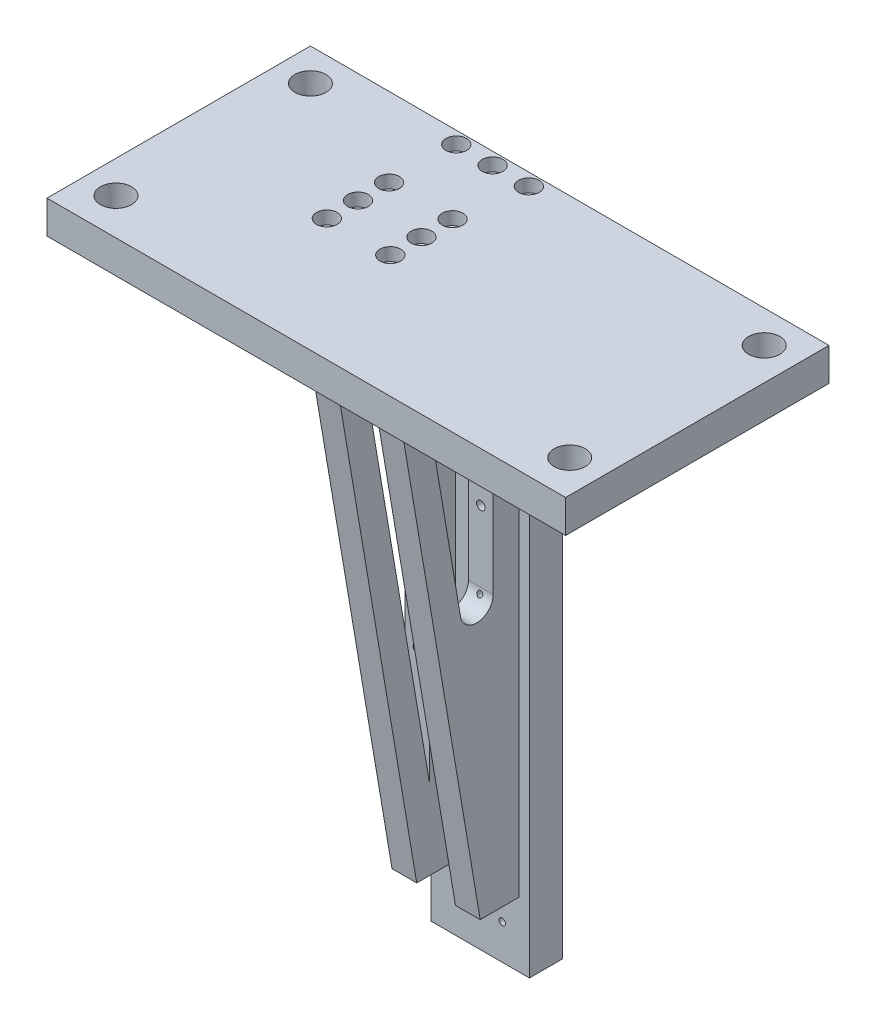
SolidWorks part; units mm, degrees
other "IGNORE"
ref_plane "Front Plane" through (0, 0, 0) normal (0, 0, 1) x (1, 0, 0)
ref_plane "Top Plane" through (0, 0, 0) normal (0, 1, 0) x (1, 0, 0)
ref_plane "Right Plane" through (0, 0, 0) normal (1, 0, 0) x (0, 0, -1)
sketch "Sketch1" plane through (0, 0, 0) normal (1, 0, 0) x (0, 0, -1)
  line L0 (-92.075, 0) -> (9.525, 0)
  line L2 (0, 0) -> (9.525, 0)
  line L4 (9.525, 9.525) -> (-92.075, 9.525)
  line L5 (-92.075, 9.525) -> (-92.075, 0)
  line L7 (0, 0) -> (9.525, 0)
  line L8 (0, 0) -> (0, -250)
  line L9 (0, -250) -> (9.525, -250)
  line L10 (9.525, 0) -> (9.525, -250)
  line L16 (9.525, 9.525) -> (9.525, 0)
  line L17 (-5.005, 0) -> (-5.005, -3.175)
  line L19 (-92.075, 0) -> (-92.075, -3.175)
  line L20 (-92.075, -3.175) -> (9.525, -3.175)
  dimension "D1" = 9.525
  dimension "D2" = 9.525
  dimension "D3" = 101.6
  dimension "D5" = 250
  dimension "D7" = 12.7
  dimension "14.53" = 14.53
extrude "Boss-Extrude5" add sketch "Sketch1" along normal blind 125 and the other way blind 75 contours L16 L4 L5 L0 | L19 L20 L17 L0 region at (0, 4.7625, 41.275) region at (0, -1.5875, 48.54)
extrude "Boss-Extrude6" add sketch "Sketch1<5>" along normal mid plane 38 separate body contours L10 L0 L8 L9 | L8 L20 L10 L0 region at (0, -1.5875, -4.7625) region at (0, -126.5875, -4.7625)
sketch "Sketch1<5>" plane through (0, 0, 0) normal (1, 0, 0) x (0, 0, -1) same geometry as "Sketch1"
sketch "Sketch2" plane through (0, 0, -9.525) normal (0, 0, -1) x (-1, 0, 0)
  line L0 (0, 0) -> (0, -263.8174) construction
  line L1 (-19, 0) -> (-15, 0)
  line L2 (-15, -4.5282) -> (15, -4.5282)
  line L3 (-15, -4.5282) -> (-15, -36.0894)
  line L4 (-15, -36.0894) -> (15, -36.0894)
  line L5 (15, -4.5282) -> (15, -36.0894)
  line L6 (-19, 0) -> (19, 0) construction
  line L7 (-15, 0) -> (-15, -250)
  line L8 (-19, -250) -> (19, -250) construction
  line L9 (-15, -250) -> (-19, -250)
  line L10 (-19, -250) -> (-19, 0)
  line M8 (19, 0) -> (-19, 0)
  line M9 (-19, 0) -> (-19, -250)
  line M10 (-19, -250) -> (19, -250)
  dimension "D1" = 30
  dimension "D2" = 4
extrude "Boss-Extrude7" add sketch "Sketch2" along normal blind 3.175 contours L7 L3 M8 M9 M10 region at (17, -125, -9.525)
sketch "Sketch6" plane through (0, 0, 0) normal (0, -1, 0) x (1, 0, 0)
  line L0 (19, 0) -> (-19, 0) construction
  line L1 (-10, 5.005) -> (10, 5.005)
  line L2 (-10, 5.005) -> (-10, 0)
  line L3 (-10, 0) -> (10, 0)
  line L4 (10, 5.005) -> (10, 0)
  line L5 (0, 0) -> (0, 18.4937) construction
  line L6 (0, -9.525) -> (0, 92.075) construction
  line L7 (19, 0) -> (19, -12.7) construction
  line L8 (19, -2.525) -> (24, -2.525)
  line L9 (19, -2.525) -> (19, -7.525)
  line L10 (19, -7.525) -> (24, -7.525)
  line L11 (24, -2.525) -> (24, -7.525)
  line L12 (-75, -9.525) -> (125, -9.525) construction
  line L13 (-75, 5.005) -> (125, 5.005) construction
  dimension "D2" = 20
  dimension "D3" = 2
  dimension "D4" = 5
  dimension "D5" = 5
extrude "Boss-Extrude8" add sketch "Sketch6" along normal up to vertex (3.175 mm away) up to point (0, -3.175, 92.075)
sketch "Sketch3" plane through (0, 0, 0) normal (0, 1, 0) x (1, 0, 0)
  line L0 (0, 0) -> (0, 9.525) construction
  line L1 (-19, 4.7625) -> (19, 4.7625) construction
  line L2 (-19, 0) -> (-19, 9.525) construction
  line L3 (19, 0) -> (19, 12.7) construction
  line L4 (0, 8.8001) -> (0, 1.2807) construction
  circle A0 centre (-14, 4.7625) radius 2
  circle A1 centre (0, 4.7625) radius 2
  circle A2 centre (14, 4.7625) radius 2
  dimension "D1" = 4
  dimension "D2" = 14
sketch "Sketch7" plane through (0, 0, -9.525) normal (0, 0, -1) x (-1, 0, 0)
  line L0 (-15, 0) -> (-15, -250) construction
  line L1 (-15, -10.1116) -> (-5.475, -10.1116)
  line L2 (-15, -10.1116) -> (-15, -28.0084)
  line L3 (-15, -28.0084) -> (-5.475, -28.0084)
  line L4 (-5.475, -10.1116) -> (-5.475, -28.0084)
  line L5 (9.475, -9.6486) -> (19, -9.6486)
  line L6 (9.475, -9.6486) -> (9.475, -28.9758)
  line L7 (9.475, -28.9758) -> (19, -28.9758)
  line L8 (19, -9.6486) -> (19, -28.9758)
  line L9 (19, 0) -> (19, -250) construction
  dimension "D1" = 9.525
sketch "Sketch5" plane through (0, 0, 0) normal (1, 0, 0) x (0, 0, -1)
  line L0 (-50.8, -3.175) -> (-50.8, -13.175)
  line L1 (-25, -3.175) -> (-25, -11.825)
  line L2 (-50.8, -13.175) -> (-15, -225)
  line L3 (-15, -225) -> (0, -225)
  line L4 (0, 0) -> (0, -250) construction
  line L5 (0, -225) -> (0, -3.175)
  line L6 (0, -3.175) -> (-50.8, -3.175)
  line L7 (0, -250) -> (9.525, -250) construction
  line L9 (-15, -3.175) -> (-15, -11.825)
  line L10 (-8.65, -18.175) -> (0, -18.175)
  line L11 (-8.65, -28.175) -> (0, -28.175)
  line L12 (-40.6582, -13.175) -> (-10, -194.5764)
  line L13 (-10, -194.5764) -> (-10, -194.5764)
  line L14 (-10, -194.5764) -> (-10, -28.1192)
  line L16 (-40.6582, -13.175) -> (-40.6582, -13.175)
  line L17 (-24.9442, -13.175) -> (-40.6582, -13.175)
  line L18 (-10, -13.175) -> (-40.6582, -13.175) construction
  line L19 (-10, -194.5764) -> (-10, -13.175) construction
  line L20 (-92.075, -3.175) -> (-5.005, -3.175) construction
  arc A0 (-15, -11.825) -> (-8.65, -18.175) centre (-8.65, -11.825) ccw
  arc A1 (-25, -11.825) -> (-8.65, -28.175) centre (-8.65, -11.825) ccw
  point P18 (-15, -18.175)
  dimension "D8" = 6.35
  dimension "D1" = 50.8
  dimension "D2" = 15
  dimension "D3" = 25
  dimension "D4" = 10
  dimension "D5" = 221.825
  dimension "D6" = 15
  dimension "D7" = 15
  dimension "D9" = 10
  dimension "D10" = 10
extrude "Boss-Extrude9" add sketch "Sketch5" along normal up to vertex (15 mm away) from vertex separate body contours L10 L9 L6 L0 L2 L3 L5 | L1 A1 L11 L5 L10 A0 L9 L6 region at (0, -5.4507, 37.9) region at (0, -17.4592, 14.2842) up to point (15, -28.0084, -9.525) starting at point (5.475, -28.0084, -9.525)
extrude "Boss-Extrude10" add sketch "Sketch5<3>" against normal up to vertex (19 mm away) from vertex separate body contours L10 L9 L6 L0 L2 L3 L5 | L1 A1 L11 L5 L10 A0 L9 L6 region at (0, -5.4507, 37.9) region at (0, -17.4592, 14.2842) up to point (-19, -9.6486, -9.525) starting at point (-9.475, -9.6486, -9.525)
sketch "Sketch5<3>" plane through (0, 0, 0) normal (1, 0, 0) x (0, 0, -1) same geometry as "Sketch5"
fillet "Fillet1" radius 6.35 4 edges at (10.2375, -194.5764, 10) (10.2375, -28.1192, 10) (10.2375, -13.175, 24.9442) (10.2375, -13.175, 40.6582)
ref_plane "Plane1" through (-2, 0, 0) normal (1, 0, 0) x (0, 0, -1)
sketch "Sketch9" plane through (0, 0, 0) normal (0, 0, -1) x (-1, 0, 0)
  line L0 (-10.2375, -18.175) -> (-10.2375, -225) construction
  line L1 (-15, -18.175) -> (-5.475, -18.175) construction
  line L2 (-15, -225) -> (-5.475, -225) construction
  line L3 (-10.2375, -121.5875) -> (-10.2375, -91.5875) construction
  line L4 (2, -22.6495) -> (2, -218.2945) construction
  line L5 (2, 27.94) -> (2, -27.94) construction
  circle A0 centre (-10.2375, -121.5875) radius 3
  circle A1 centre (-10.2375, -151.5875) radius 3
  circle A2 centre (-10.2375, -181.5875) radius 3
  circle A3 centre (-10.2375, -211.5875) radius 3
  circle A16 centre (-10.2375, -91.5875) radius 3
  circle A17 centre (-10.2375, -61.5875) radius 3
  circle A18 centre (-10.2375, -31.5875) radius 3
  circle A19 centre (14.2375, -211.5875) radius 3
  circle A20 centre (14.2375, -181.5875) radius 3
  circle A21 centre (14.2375, -151.5875) radius 3
  circle A22 centre (14.2375, -121.5875) radius 3
  circle A23 centre (14.2375, -91.5875) radius 3
  circle A24 centre (14.2375, -61.5875) radius 3
  circle A25 centre (14.2375, -31.5875) radius 3
  dimension "D1" = 6
  dimension "D4" = 30
  dimension "D5" = 4
  dimension "D6" = 30
  dimension "D2" = 4
  dimension "D3" = 1
sketch "Sketch8" plane through (0, -3.175, 0) normal (0, 1, 0) x (1, 0, 0)
  line L0 (10.2375, -15) -> (10.2375, -50.8) construction
  line L1 (15, -15) -> (5.475, -15) construction
  line L2 (15, -50.8) -> (5.475, -50.8) construction
  line L3 (5.475, -32.9) -> (15, -32.9) construction
  line L4 (5.475, -15) -> (5.475, -50.8) construction
  line L5 (15, -15) -> (15, -50.8) construction
  line L7 (-2, 31.7466) -> (-2, -84.8925) construction
  line L8 (-2, -27.94) -> (-2, 27.94) construction
  circle A0 centre (10.2375, -20.9) radius 3
  circle A1 centre (10.2375, -32.9) radius 3
  circle A2 centre (10.2375, -44.9) radius 3
  circle A3 centre (-14.2375, -44.9) radius 3
  circle A4 centre (-14.2375, -32.9) radius 3
  circle A5 centre (-14.2375, -20.9) radius 3
  dimension "D2" = 6
  dimension "D1" = 12
hole_wizard "CBORE for M4 SHCS1" positions "Sketch12" profile "Sketch13" counterbore size "M4" standard "ANSI Metric" end condition through all
sketch "Sketch12" plane through (0, 0, -9.525) normal (0, 0, -1) x (-1, 0, 0)
  line L0 (-10.2375, -18.175) -> (-10.2375, -225) construction
  point P0 (-10.2375, -61.5875)
  point P3 (-10.2375, -31.5875)
  point P6 (-10.2375, -91.5875)
  point P9 (-10.2375, -121.5875)
  point P13 (-10.2375, -151.5875)
  point P16 (-10.2375, -181.5875)
  point P19 (-10.2375, -211.5875)
  point P22 (14.2375, -211.5875)
  point P25 (14.2375, -181.5875)
  point P28 (14.2375, -151.5875)
  point P31 (14.2375, -121.5875)
  point P34 (14.2375, -91.5875)
  point P37 (14.2375, -61.5875)
  point P40 (14.2375, -31.5875)
sketch "Sketch13" plane through (10.2375, -61.5875, -9.525) normal (1, 0, 0) x (0, 1, 0)
  line L0 (0, 0) -> (0, 101.6)
  line L1 (0, 101.6) -> (2.4, 101.6)
  line L3 (2.4, 101.6) -> (2.4, 5)
  line L4 (2.4, 5) -> (4, 5)
  line L5 (4, 5) -> (4, 0)
  line L7 (4, 0) -> (0, 0)
  line L11 (0, -6.35) -> (0, 107.95) construction
  dimension "Thru Hole Dia." = 4.8
  dimension "Thru Hole Depth" = 101.6
  dimension "C'Bore Dia." = 8
  dimension "C'Bore Depth" = 5
hole_wizard "CBORE for M4 SHCS2" positions "Sketch14" profile "Sketch15" counterbore size "M4" standard "ANSI Metric" end condition through all
sketch "Sketch14" plane through (0, 9.525, 0) normal (0, 1, 0) x (1, 0, 0)
  line L0 (-19, 4.7625) -> (19, 4.7625) construction
  point P0 (-14.2375, -20.9)
  point P3 (-14.2375, -32.9)
  point P6 (-14.2375, -44.9)
  point P9 (10.2375, -44.9)
  point P12 (10.2375, -32.9)
  point P15 (10.2375, -20.9)
  point P18 (14, 4.7625)
  point P21 (0, 4.7625)
  point P25 (-14, 4.7625)
sketch "Sketch15" plane through (-14.2375, 9.525, 20.9) normal (1, 0, 0) x (0, 0, 1)
  line L0 (0, 0) -> (0, 259.525)
  line L1 (0, 259.525) -> (2.4, 259.525)
  line L3 (2.4, 259.525) -> (2.4, 5)
  line L4 (2.4, 5) -> (4, 5)
  line L5 (4, 5) -> (4, 0)
  line L7 (4, 0) -> (0, 0)
  line L11 (0, -6.35) -> (0, 107.95) construction
  dimension "Thru Hole Dia." = 4.8
  dimension "Thru Hole Depth" = 259.525
  dimension "C'Bore Dia." = 8
  dimension "C'Bore Depth" = 5
hole_wizard "M4x0.7 Tapped Hole1" positions "Sketch16" profile "Sketch17" tap size "M4x0.7" standard "ANSI Metric"
sketch "Sketch16" plane through (0, -3.175, 0) normal (0, 1, 0) x (1, 0, 0)
  point P0 (10.2375, -20.9)
  point P3 (10.2375, -32.9)
  point P6 (10.2375, -44.9)
  point P9 (-14.2375, -44.9)
  point P12 (-14.2375, -32.9)
  point P15 (-14.2375, -20.9)
sketch "Sketch17" plane through (10.2375, -3.175, 20.9) normal (1, 0, 0) x (0, 0, 1)
  line L0 (0, 0) -> (0, 11.0914)
  line L1 (0, 11.0914) -> (1.65, 10.1)
  line L2 (1.65, 10.1) -> (1.65, 0)
  line L5 (1.65, 0) -> (0, 0)
  line L10 (0, 11.0914) -> (-1.65, 10.1) construction
  line L11 (0, -6.35) -> (0, 107.95) construction
  dimension "Tap Drill Dia." = 3.3
  dimension "Tap Drill Depth" = 10.1
  dimension "Drill Angle" = 118
hole_wizard "M4x0.7 Tapped Hole2" positions "Sketch18" profile "Sketch19" tap size "M4x0.7" standard "ANSI Metric"
sketch "Sketch18" plane through (0, 0, 0) normal (0, 0, -1) x (-1, 0, 0)
  line L0 (-10.2375, -18.175) -> (-10.2375, -225) construction
  point P0 (-10.2375, -31.5875)
  point P3 (14.2375, -31.5875)
  point P6 (14.2375, -61.5875)
  point P9 (-10.2375, -61.5875)
  point P12 (-10.2375, -91.5875)
  point P15 (14.2375, -91.5875)
  point P18 (-10.2375, -121.5875)
  point P22 (14.2375, -121.5875)
  point P25 (-10.2375, -151.5875)
  point P28 (14.2375, -151.5875)
  point P31 (-10.2375, -181.5875)
  point P34 (14.2375, -181.5875)
  point P37 (-10.2375, -211.5875)
  point P40 (14.2375, -211.5875)
sketch "Sketch19" plane through (10.2375, -31.5875, 0) normal (1, 0, 0) x (0, 1, 0)
  line L0 (0, 0) -> (0, 11.0914)
  line L1 (0, 11.0914) -> (1.65, 10.1)
  line L2 (1.65, 10.1) -> (1.65, 0)
  line L5 (1.65, 0) -> (0, 0)
  line L10 (0, 11.0914) -> (-1.65, 10.1) construction
  line L11 (0, -6.35) -> (0, 107.95) construction
  dimension "Tap Drill Dia." = 3.3
  dimension "Tap Drill Depth" = 10.1
  dimension "Drill Angle" = 118
sketch "Sketch20" plane through (0, 9.525, 0) normal (0, 1, 0) x (1, 0, 0)
  line L0 (25, 9.525) -> (25, -92.075) construction
  line L1 (-75, 9.525) -> (125, 9.525) construction
  line L2 (-75, -92.075) -> (125, -92.075) construction
  line L3 (-75, 9.525) -> (-75, -92.075) construction
  circle A0 centre (-62.5, -2.975) radius 5
  circle A1 centre (-62.5, -77.975) radius 5
  circle A2 centre (112.5, -77.975) radius 5
  circle A3 centre (112.5, -2.975) radius 5
  dimension "D1" = 10
  dimension "D2" = 12.5
  dimension "D3" = 12.5
  dimension "D4" = 75
sketch "Sketch23" plane through (0, 0, 0) normal (0, -1, 0) x (1, 0, 0)
  line L0 (-75, 5.005) -> (-10, 5.005) construction
  line L1 (10, 5.005) -> (125, 5.005) construction
  line L3 (125, -9.525) -> (45, -9.525)
  line L4 (-40, 5.005) -> (-75, 5.005)
  line L5 (-40, 5.005) -> (-40, -9.525)
  line L6 (-40, -9.525) -> (-75, -9.525)
  line L7 (-75, 5.005) -> (-75, -9.525)
  line L8 (125, -9.525) -> (125, 5.005)
  line L9 (125, 5.005) -> (45, 5.005)
  line L10 (45, -9.525) -> (45, 5.005)
  dimension "D1" = 35
  dimension "50" = 80
fillet "Fillet2" radius 6.35 2 edges at (10, -1.5875, 5.005) (-10, -1.5875, 5.005)
extrude "Boss-Extrude11" add sketch "Sketch23" along normal up to surface (3.175 mm away) up to face at (-14.2375, -3.175, 18.5)
hole_wizard "M10 Clearance Hole1" positions "Sketch21" profile "Sketch22" hole size "M10" standard "ANSI Metric" end condition through all
sketch "Sketch21" plane through (0, 9.525, 0) normal (0, 1, 0) x (1, 0, 0)
  point P0 (-62.5, -2.975)
  point P3 (-62.5, -77.975)
  point P6 (112.5, -77.975)
  point P9 (112.5, -2.975)
sketch "Sketch22" plane through (-62.5, 9.525, 2.975) normal (1, 0, 0) x (0, 0, 1)
  line L0 (0, 0) -> (0, 259.525)
  line L1 (0, 259.525) -> (6, 259.525)
  line L2 (6, 259.525) -> (6, 0)
  line L5 (6, 0) -> (0, 0)
  line L11 (0, -6.35) -> (0, 107.95) construction
  dimension "Thru Hole Dia." = 12
  dimension "Thru Hole Depth" = 259.525
fillet "Fillet3" radius 6.35 2 edges at (45, -1.5875, 5.005) (-40, -1.5875, 5.005)
hole_wizard "M4x0.7 Tapped Hole3" positions "Sketch24" profile "Sketch25" tap size "M4x0.7" standard "ANSI Metric"
sketch "Sketch24" plane through (0, 0, 0) normal (0, 1, 0) x (1, 0, 0)
  point P0 (-14, 4.7625)
  point P3 (0, 4.7625)
  point P6 (14, 4.7625)
sketch "Sketch25" plane through (-14, 0, -4.7625) normal (1, 0, 0) x (0, 0, 1)
  line L0 (0, 0) -> (0, 11.0914)
  line L1 (0, 11.0914) -> (1.65, 10.1)
  line L2 (1.65, 10.1) -> (1.65, 0)
  line L5 (1.65, 0) -> (0, 0)
  line L10 (0, 11.0914) -> (-1.65, 10.1) construction
  line L11 (0, -6.35) -> (0, 107.95) construction
  dimension "Tap Drill Dia." = 3.3
  dimension "Tap Drill Depth" = 10.1
  dimension "Drill Angle" = 118
sketch "Sketch26" plane through (0, 0, -9.525) normal (0, 0, -1) x (-1, 0, 0)
  line L0 (0, -11.1171) -> (0, -57.3944) construction
  line L1 (-15, 0) -> (-15, -250) construction
  line L2 (40, 0) -> (-45, 0) construction
  circle A0 centre (-8.5, -11.475) radius 1.5
  circle A1 centre (8.5, -11.475) radius 1.5
  circle A2 centre (-8.5, -236.475) radius 1.5
  circle A3 centre (8.5, -236.475) radius 1.5
  point P12 (0, 0)
  point P13 (0, 0)
  dimension "D2" = 3
  dimension "D1" = 15
  dimension "D3" = 17
  dimension "D4" = 11.475
  dimension "D5" = 225
hole_wizard "M3x0.5 Tapped Hole1" positions "Sketch27" profile "Sketch28" tap size "M3x0.5" standard "ANSI Metric" end condition through all
sketch "Sketch27" plane through (0, 0, -9.525) normal (0, 0, -1) x (-1, 0, 0)
  point P0 (-8.5, -11.475)
  point P3 (8.5, -11.475)
  point P6 (-8.5, -236.475)
  point P9 (8.5, -236.475)
sketch "Sketch28" plane through (8.5, -11.475, -9.525) normal (1, 0, 0) x (0, 1, 0)
  line L0 (0, 0) -> (0, 101.6)
  line L1 (0, 101.6) -> (1.25, 101.6)
  line L2 (1.25, 101.6) -> (1.25, 0)
  line L5 (1.25, 0) -> (0, 0)
  line L11 (0, -6.35) -> (0, 107.95) construction
  dimension "Thru Tap Drill Dia." = 2.5
  dimension "Thru Tap Drill Depth" = 101.6
cosmetic thread "Hole Thread1" parameters "D2"=3
cosmetic thread "Hole Thread2" parameters "D2"=3
cosmetic thread "Hole Thread3" parameters "D2"=3
cosmetic thread "Hole Thread4" parameters "D2"=3
